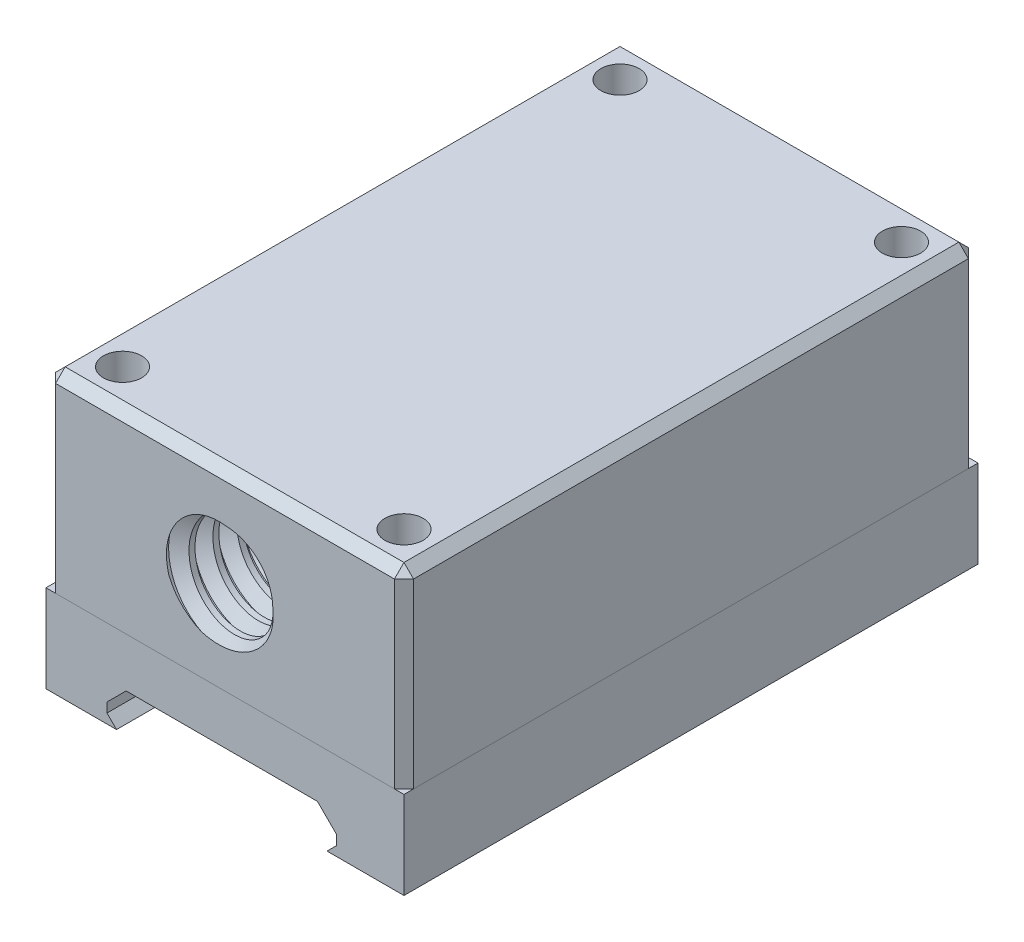
SolidWorks part; units mm, degrees
ref_plane "Front Plane" through (0, 0, 0) normal (0, 0, 1) x (1, 0, 0)
ref_plane "Top Plane" through (0, 0, 0) normal (0, 1, 0) x (1, 0, 0)
ref_plane "Right Plane" through (0, 0, 0) normal (1, 0, 0) x (0, 0, -1)
sketch "Sketch2" plane through (0, 0, 0) normal (0, 0, 1) x (1, 0, 0)
  line L1 (-0.1583, 0.5133) -> (-0.1583, 5.0895)
  line L3 (18.5523, 5.0895) -> (18.5523, 0.5133)
  line L7 (14.5294, 0.5133) -> (15.0294, 1.0133)
  line L8 (15.0294, 1.0133) -> (15.0294, 1.5133)
  line L9 (15.0294, 1.5133) -> (14.0294, 2.5133)
  line L10 (14.0294, 2.5133) -> (4.0294, 2.5133)
  line L11 (4.0294, 2.5133) -> (3.0294, 1.5133)
  line L12 (3.0294, 1.5133) -> (3.0294, 1.0133)
  line L13 (3.0294, 1.0133) -> (3.5294, 0.5133)
  line L16 (-0.1583, 5.0895) -> (18.5523, 5.0895)
  line L17 (3.5294, 0.5133) -> (-0.1583, 0.5133)
  line L18 (14.5294, 0.5133) -> (18.5523, 0.5133)
extrude "Boss-Extrude2" add sketch "Sketch2" along normal blind 30
sketch "Sketch4" plane through (0, 5.0895, 0) normal (0, 1, 0) x (1, 0, 0)
  line L1 (-0.1583, 0) -> (18.5523, 0)
  line L2 (-0.1583, 0) -> (-0.1583, -30)
  line L3 (-0.1583, -30) -> (18.5523, -30)
  line L4 (18.5523, 0) -> (18.5523, -30)
extrude "Boss-Extrude3" add sketch "Sketch4" along normal blind 10 separate body
sketch "Sketch5" plane through (0, 0, 30) normal (0, 0, 1) x (1, 0, 0)
  line L0 (-0.1583, 15.0895) -> (18.5523, 5.0895) construction
  circle A0 centre (9.197, 10.0895) radius 2.5
extrude "Cut-Extrude2" cut sketch "Sketch5" against normal blind 30
sketch "Sketch6" plane through (0, 15.0895, 0) normal (0, 1, 0) x (1, 0, 0)
  line L0 (18.5523, 0) -> (-0.1583, 0) construction
  line L1 (-0.1583, 0) -> (-0.1583, -30) construction
  line L2 (18.5523, -30) -> (18.5523, 0) construction
  line L3 (-0.1583, -30) -> (18.5523, -30) construction
  circle A0 centre (1.8417, -2) radius 1
  circle A1 centre (16.5523, -2) radius 1
  circle A2 centre (1.8417, -28) radius 1
  circle A3 centre (16.5523, -28) radius 1
  dimension "D1" = 2
  dimension "D2" = 2
  dimension "D3" = 2
  dimension "D4" = 2
  dimension "D5" = 2
  dimension "D6" = 2
  dimension "D7" = 2
  dimension "D8" = 2
  dimension "D9" = 2
extrude "Cut-Extrude3" cut sketch "Sketch6" against normal blind 5
sketch "Sketch9" plane through (0, 15.0895, 0) normal (0, 1, 0) x (1, 0, 0)
  line L0 (9.197, 0) -> (9.197, 10) construction
  line L1 (18.5523, 0) -> (-0.1583, 0) construction
  dimension "D1" = 10
chamfer "Chamfer2" distance 0.5 angle 45 8 edges at (-0.1583, 10.0895, 0) (9.197, 15.0895, 0) (18.5523, 10.0895, 0) (-0.1583, 15.0895, 15) (18.5523, 15.0895, 15) (18.5523, 10.0895, 30) (9.197, 15.0895, 30) (-0.1583, 10.0895, 30)
thread "Thread2" pitch 1.25 profile "Thread Profile3" start angle 0, offset 0, length 50, pitch 1.25, diameter 5
ref_plane "Plane3" through (11.697, 10.0895, -10) normal (0, -1, 0) x (1, 0, 0)
sketch "Thread Profile3" plane through (11.697, 10.0895, -10) normal (0, -1, 0) x (1, 0, 0)
  line L0 (0, 0) -> (0, 1.25) construction
  line L1 (0, 0) -> (0.6766, 0.3906)
  line L2 (0.6766, 0.3906) -> (0.6766, 0.5469)
  line L3 (0.6766, 0.5469) -> (0, 0.9375)
  line L4 (0.6766, 0.4687) -> (0, 0.4687) construction
  line L11 (0, 0) -> (0, 0.9375)
  point P2 (0, 0)
  dimension "Pitch" = 1.25
  dimension "Profile_Angle" = 60
  dimension "Profile_Land" = 0.1562
  dimension "Profile_Height" = 0.6766
